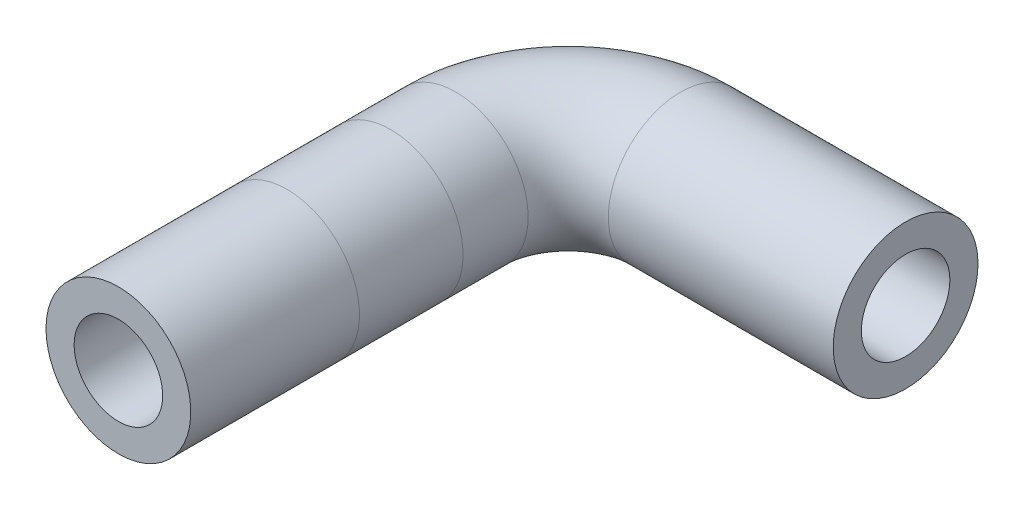
SolidWorks part; units mm, degrees
material "Silicon Rubber"
ref_plane "X-Y Datum" through (0, 0, 0) normal (0, 0, 1) x (1, 0, 0)
ref_plane "X-Z Datum" through (0, 0, 0) normal (0, 1, 0) x (1, 0, 0)
ref_plane "Y-Z Datum" through (0, 0, 0) normal (1, 0, 0) x (0, 0, -1)
sketch3d "3DSketch1"
  line L0 (-39.4506, 0, -7.35) -> (-39.4506, 0, 0)
  line L1 (-39.4506, 0, 0) -> (-39.4506, 0, 11.7)
  line L2 (-39.4506, 0, 30.75) -> (-39.4506, 0, 11.7)
  line L3 (-26.7506, 0, -20.05) -> (-1.3506, 0, -20.05)
  arc A1 (-39.4506, 0, -7.35) -> (-26.7506, 0, -20.05) centre (-26.7506, 0, -7.35) cw
  circle A3 centre (-39.4506, 0, 11.7) radius 5 construction
  point P3 (-26.7506, -12.7, -7.35)
  point P7 (-39.4506, 0, 16.7)
  dimension "D2" = 12.7
  dimension "D5" = 10
  dimension "D1" = 38.1
  dimension "D3" = 90
  dimension "D4" = 25.4
  dimension "D6" = 19.05
sweep "Sweep1" add path "3DSketch1" circular profile diameter 16.35 parameters "D3"=16.35
sweep "Cut-Sweep1" cut path "3DSketch1<2>" circular profile diameter 10 parameters "D3"=10
sketch3d "3DSketch1<2>" same geometry as "3DSketch1"
sketch3d "3DSketch2"
  circle A0 centre (-39.4506, 0, 11.7) radius 5 construction
  circle A1 centre (-39.4506, 0, 11.7) radius 8.175 construction
  circle A2 centre (-39.4506, 0, 30.75) radius 5 construction
  point P2 (-39.4506, 0, 16.7)
  point P5 (-39.4506, 0, 3.525)
  point P8 (-39.4506, 0, 35.75)
